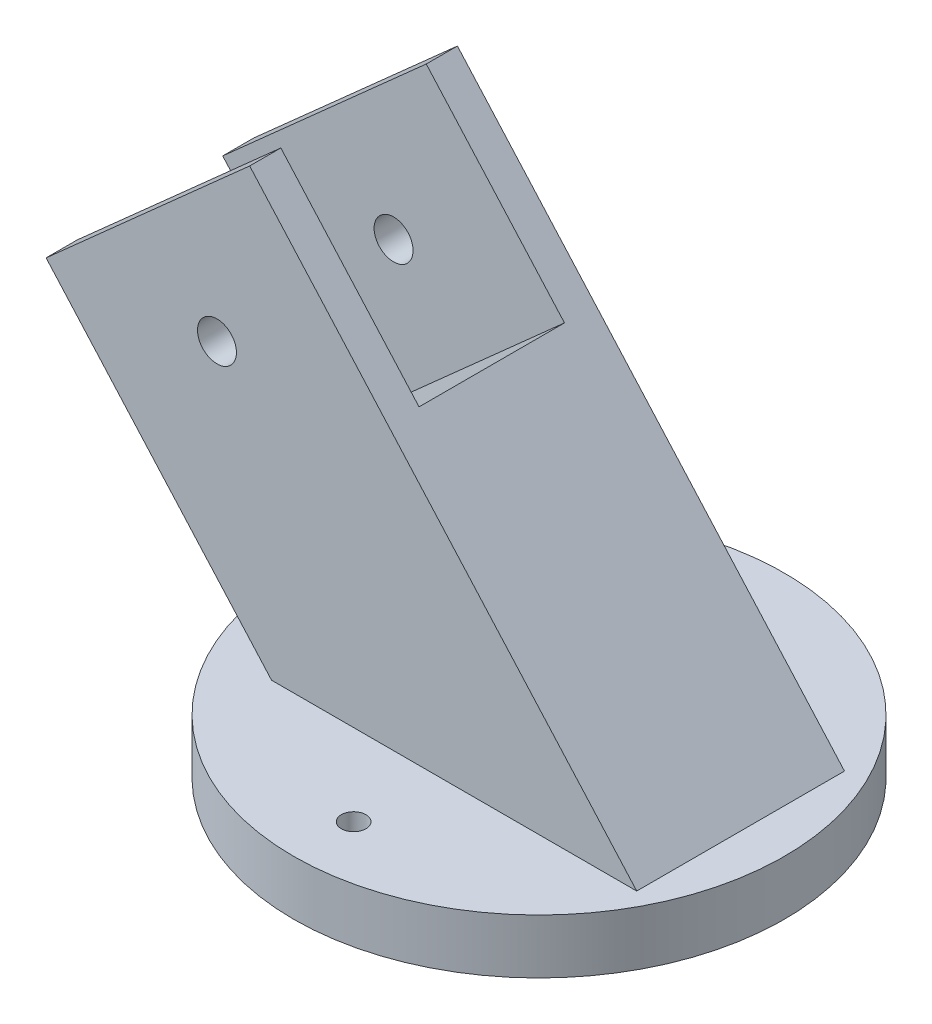
SolidWorks part; units mm, degrees
ref_plane "Front Plane" through (0, 0, 0) normal (0, 0, 1) x (1, 0, 0)
ref_plane "Top Plane" through (0, 0, 0) normal (0, 1, 0) x (1, 0, 0)
ref_plane "Right Plane" through (0, 0, 0) normal (1, 0, 0) x (0, 0, -1)
sketch "Sketch1" plane through (0, 0, 0) normal (0, 1, 0) x (1, 0, 0)
  circle A0 centre (0, 0) radius 45
  circle A1 centre (0, 34) radius 2.25
  circle A2 centre (0, -34) radius 2.25
  dimension "D1" = 90
  dimension "D3" = 4.5
  dimension "D2" = 34
  dimension "D4" = 34
extrude "Boss-Extrude1" add sketch "Sketch1" along normal blind 10
sketch "Sketch2" plane through (0, 0, 0) normal (0, 0, 1) x (1, 0, 0)
  line L0 (36.9668, 10) -> (-34.0134, 89.6664)
  line L1 (45, 10) -> (-45, 10) construction
  line L2 (-30, 10) -> (-71.3453, 56.4049)
  line L3 (-45, 10) -> (-45, 0) construction
  line L4 (-30, 10) -> (36.9668, 10)
  line L5 (-46, 27.958) -> (-8.6681, 61.2195) construction
  line L6 (-71.3453, 56.4049) -> (-34.0134, 89.6664)
  line L7 (-40.0067, 58.8122) -> (-52.6793, 73.0357) construction
  point P8 (-46, 27.958)
  point P11 (-40.0067, 58.8122)
  dimension "D1" = 48.3
  dimension "D2" = 50
  dimension "D3" = 15
  dimension "D4" = 1
  dimension "D5" = 38.1
  dimension "D6" = 19.05
extrude "Boss-Extrude2" add sketch "Sketch2" along normal blind 19.05 and the other way blind 19.05
sketch "Sketch3" plane through (-59.5881, 66.8802, 0) normal (-0.6652, 0.7466, 0) x (0.7466, 0.6652, 0)
  line L0 (-15.7468, 19.05) -> (-15.7468, -19.05) construction
  line L1 (-15.7468, 13.335) -> (34.2532, 13.335)
  line L2 (-15.7468, 13.335) -> (-15.7468, -13.335)
  line L3 (-15.7468, -13.335) -> (34.2532, -13.335)
  line L4 (34.2532, 13.335) -> (34.2532, -13.335)
  line L5 (34.2532, 19.05) -> (34.2532, -19.05) construction
  line L6 (-15.7468, 19.05) -> (-15.7468, -19.05) construction
  point P8 (-15.7468, 0)
  dimension "D1" = 26.67
extrude "Cut-Extrude1" cut sketch "Sketch3" against normal blind 38.1
hole_wizard "1/4 Clearance Hole1" positions "Sketch4" profile "Sketch5" hole size "1/4" standard "ANSI Inch" end condition through all
sketch "Sketch4" plane through (0, 0, 19.05) normal (0, 0, 1) x (1, 0, 0)
  point P0 (-40.0067, 58.8122)
sketch "Sketch5" plane through (-40.0067, 58.8122, 19.05) normal (1, 0, 0) x (0, -1, 0)
  line L0 (0, 0) -> (0, 64.05)
  line L1 (0, 64.05) -> (3.5712, 64.05)
  line L2 (3.5712, 64.05) -> (3.5712, 0)
  line L5 (3.5712, 0) -> (0, 0)
  line L11 (0, -6.35) -> (0, 107.95) construction
  dimension "Thru Hole Dia." = 7.1425
  dimension "Thru Hole Depth" = 64.05
